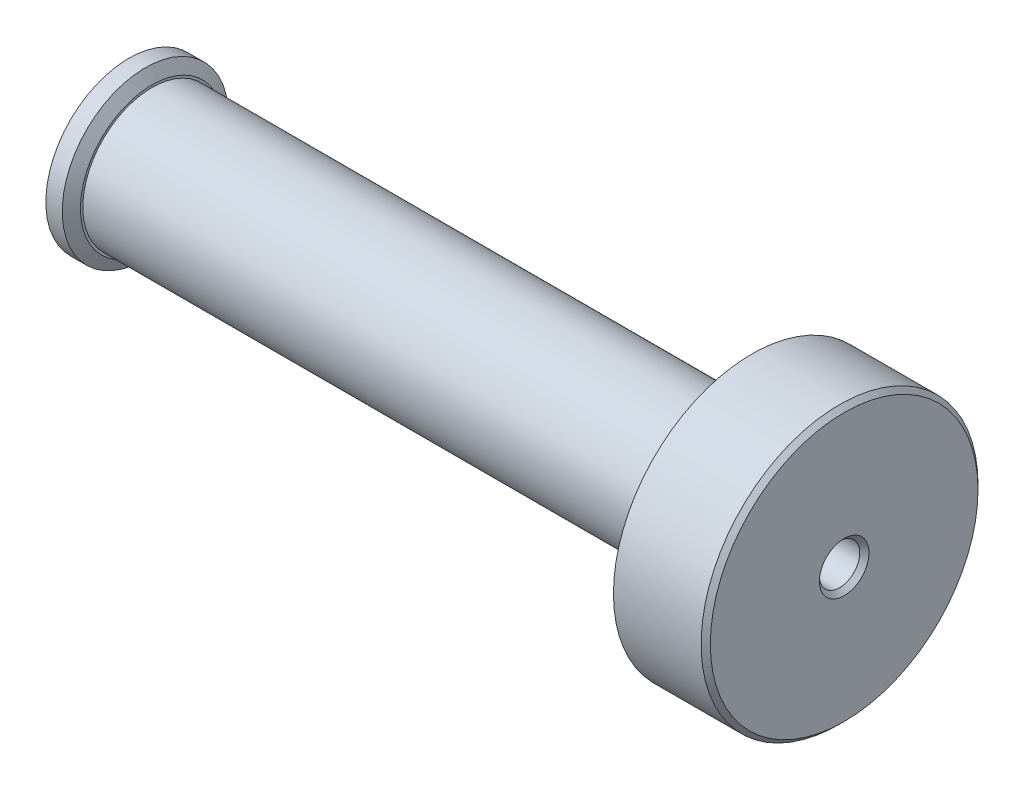
SolidWorks part; units mm, degrees
material "Custom Plastic"
ref_plane "Front Plane" through (0, 0, 0) normal (0, 0, 1) x (1, 0, 0)
ref_plane "Top Plane" through (0, 0, 0) normal (0, 1, 0) x (1, 0, 0)
ref_plane "Right Plane" through (0, 0, 0) normal (1, 0, 0) x (0, 0, -1)
sketch "Sketch3" plane through (0, 0, 0) normal (0, 1, 0) x (1, 0, 0)
  line L0 (0, 0) -> (-62, 0) construction
  line L1 (-62, 0) -> (-62, 7.2)
  line L2 (-62, 7.2) -> (-60, 7.2)
  line L3 (-60, 7.2) -> (-60, 6)
  line L4 (-60, 6) -> (-10, 6)
  line L5 (-10, 6) -> (-10, 12)
  line L6 (-10, 12) -> (0, 12)
  line L7 (0, 12) -> (0, 0)
  line L8 (0, 0) -> (-62, 0)
  dimension "D1" = 24
  dimension "D2" = 12
  dimension "D3" = 10
  dimension "D4" = 50
  dimension "D5" = 2
  dimension "D6" = 1.2
revolve "Revolve1" add sketch "Sketch3" angle 360 about L0
chamfer "Chamfer1" distance 1 angle 30 1 edges at (-60, 0, -7.2) first distance on face at (-60, 0, -7.2)
chamfer "Chamfer2" distance 2 angle 60 1 edges at (-10, 0, -12) first distance on face at (-10, 0, -12)
sketch "Sketch4" plane through (-62, 0, 0) normal (-1, 0, 0) x (0, 0, 1)
  circle A0 centre (0, 0) radius 4.8
  circle A1 centre (0, 0) radius 6 construction
  dimension "D1" = 1.2
extrude "Cut-Extrude1" cut sketch "Sketch4" against normal offset from surface (53 mm away) 9 up to face at (0, 0, -12)
sketch "Sketch5" plane through (-9, 0, 0) normal (-1, 0, 0) x (0, 0, 1)
  circle A0 centre (0, 0) radius 1.75
  dimension "D1" = 3.5
extrude "Cut-Extrude2" cut sketch "Sketch5" against normal through all
chamfer "Chamfer3" distance 0.4 angle 45 2 edges at (0, 0, -12) (0, 0, 1.75)
